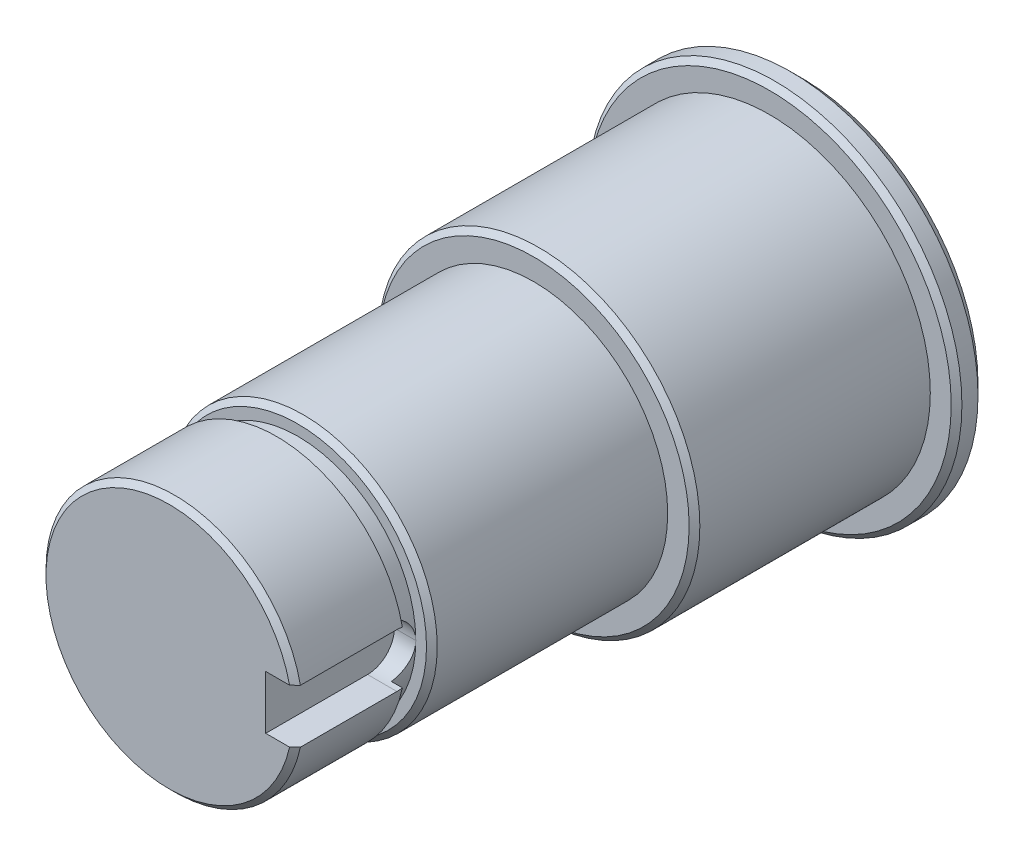
SolidWorks part; units mm, degrees
ref_plane "前视基准面" through (0, 0, 0) normal (0, 0, 1) x (1, 0, 0)
ref_plane "上视基准面" through (0, 0, 0) normal (0, 1, 0) x (1, 0, 0)
ref_plane "右视基准面" through (0, 0, 0) normal (1, 0, 0) x (0, 0, -1)
sketch "草图1" plane through (0, 0, 0) normal (0, 0, 1) x (1, 0, 0)
  circle A0 centre (0, 0) radius 17.45
extrude "拉伸1" add sketch "草图1" along normal blind 3
sketch "草图2" plane through (0, 0, 3) normal (0, 0, 1) x (1, 0, 0)
  circle A0 centre (0, 0) radius 15
  dimension "D1" = 30
extrude "拉伸2" add sketch "草图2" along normal blind 22
sketch "草图4" plane through (0, 0, 25) normal (0, 0, 1) x (1, 0, 0)
  circle A0 centre (0, 0) radius 12.5
extrude "拉伸3" add sketch "草图4" along normal blind 22
sketch "草图5" plane through (0, 0, 47) normal (0, 0, 1) x (1, 0, 0)
  circle A0 centre (0, 0) radius 12
extrude "拉伸4" add sketch "草图5" along normal blind 12
chamfer "倒角1" distance 0.5 angle 45 1 edges at (12, 0, 59)
sketch "草图6" plane through (0, 0, 0) normal (0, 1, 0) x (1, 0, 0)
  line L1 (-12, -47) -> (-11, -47)
  line L2 (-12, -47) -> (-12, -49)
  line L3 (-12, -49) -> (-11, -49)
  line L4 (-11, -47) -> (-11, -49)
  dimension "D1" = 1
  dimension "D2" = 2
ref_axis "基准轴1" through (0, 0, 47) along (0, 0, -1)
revolve "切除-旋转1" cut sketch "草图6" angle 360 about axis through (0, 0, 47) along (0, 0, -1)
chamfer "倒角2" distance 0.5 angle 45 3 edges at (17.45, 0, 3) (15, 0, 25) (12.5, 0, 47)
chamfer "倒角3" distance 1 angle 45 1 edges at (17.45, 0, 0)
ref_plane "基准面1" through (12, 0, 0) normal (1, 0, 0) x (0, 0, -1)
sketch "草图7" plane through (12, 0, 0) normal (1, 0, 0) x (0, 0, -1)
  line L0 (-59, 11.5) -> (-59, -11.5) construction
  line L1 (-59, 2.5) -> (-47, 2.5)
  line L2 (-59, 2.5) -> (-59, -2.5)
  line L3 (-59, -2.5) -> (-47, -2.5)
  line L4 (-47, 2.5) -> (-47, -2.5)
  line L5 (-47, 11) -> (-47, -11) construction
extrude "切除-拉伸1" cut sketch "草图7" against normal blind 3
fillet "圆角1" radius 2.5 2 edges at (9.8561, -2.5, 47) (9.8561, 2.5, 47)
